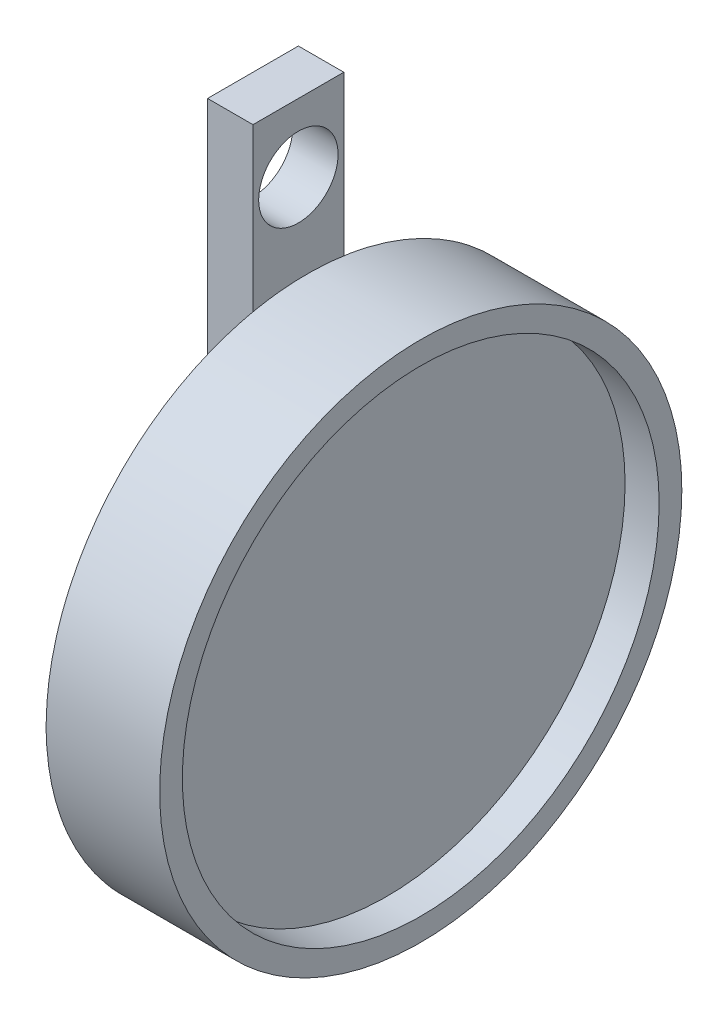
SolidWorks part; units mm, degrees
material "PLA"
ref_plane "Front Plane" through (0, 0, 0) normal (1, 0, 0) x (0, 1, 0)
ref_plane "Top Plane" through (0, 0, 0) normal (0, 0, 1) x (0, 1, 0)
ref_plane "Right Plane" through (0, 0, 0) normal (0, 1, 0) x (-1, 0, 0)
sketch "Sketch1" plane through (0, 0, 0) normal (1, 0, 0) x (0, 1, 0)
  circle A0 centre (0, 0) radius 11.5
  circle A1 centre (0, 0) radius 10.5
  dimension "D1" = 1
  dimension "D2" = 21
extrude "Boss-Extrude1" add sketch "Sketch1" along normal blind 5
extrude "Boss-Extrude2" add sketch "Sketch1<2>" along normal blind 3.5 contours A1 region at (0, 0, 0)
sketch "Sketch1<2>" plane through (0, 0, 0) normal (1, 0, 0) x (0, 1, 0) same geometry as "Sketch1"
ref_plane "Plane1" through (-2.39, 0, 0) normal (-1, 0, 0) x (0, 0, 1)
sketch "Sketch2" plane through (-2.39, 0, 0) normal (-1, 0, 0) x (0, 0, 1)
  line L1 (-2, -5) -> (2, -5)
  line L2 (-2, -5) -> (-2, 5)
  line L3 (-2, 5) -> (2, 5)
  line L4 (2, -5) -> (2, 5)
  line L5 (0, 5) -> (0, -5) construction
  line L6 (-2, 0) -> (2, 0) construction
  point P0 (0, 0)
  dimension "D1" = 4
  dimension "D2" = 10
sketch "Sketch3" plane through (0, 0, 0) normal (-1, 0, 0) x (0, -1, 0)
  circle A0 centre (0, 0) radius 11.5
  circle A1 centre (0, 0) radius 9.5
  circle A2 centre (0, 0) radius 11.5 construction
  dimension "D1" = 2
extrude "Cut-Extrude2" cut sketch "Sketch3" against normal blind 1.5 contours A1 region at (0, 0, 0)
sketch "Sketch4" plane through (0, 0, 0) normal (-1, 0, 0) x (0, -1, 0)
  circle A1 centre (0, 0) radius 11.5
  circle A2 centre (0, 0) radius 11.5
  dimension "D1" = 0
loft "Loft1" add profiles "Sketch4", "Sketch2" connector at (0, 0, 11.5) connector at (-2.39, -5, -2)
sketch "Sketch6" plane through (-2.39, 0, 0) normal (-1, 0, 0) x (0, -1, 0)
  line L0 (0, 0) -> (-15, 0) construction
  line L1 (5, 2) -> (-18, 2)
  line L2 (-18, 2) -> (-18, -2)
  line L3 (-18, -2) -> (5, -2)
  line L4 (5, -2) -> (5, 2)
  circle A1 centre (-15, 0) radius 1.75
  point P1 (0, 0)
  dimension "D2" = 3.5
  dimension "D1" = 15
  dimension "D3" = 3
extrude "Boss-Extrude3" add sketch "Sketch6" against normal blind 2
